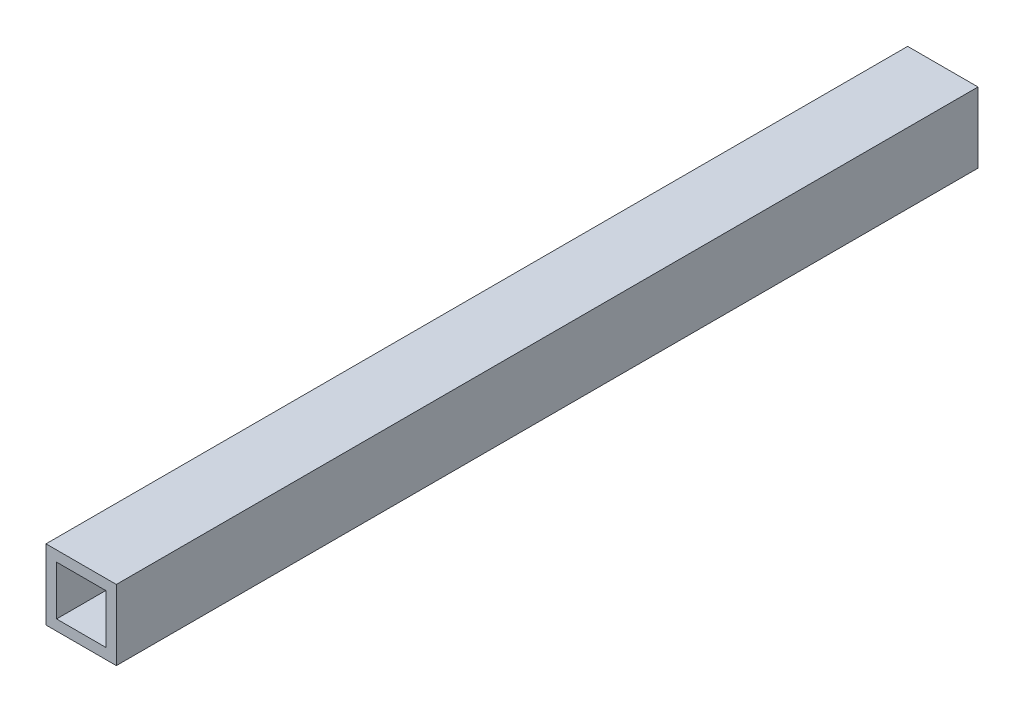
SolidWorks part; units mm, degrees
ref_plane "前视基准面" through (0, 0, 0) normal (0, 0, 1) x (1, 0, 0)
ref_plane "上视基准面" through (0, 0, 0) normal (0, 1, 0) x (1, 0, 0)
ref_plane "右视基准面" through (0, 0, 0) normal (1, 0, 0) x (0, 0, -1)
other "Configuration Table"
sketch "草图1" plane through (0, 0, 0) normal (0, 0, 1) x (1, 0, 0)
  line L0 (-9.3333, 11.0061) -> (-9.3333, -8.9939)
  line L1 (-9.3333, 11.0061) -> (10.6667, 11.0061)
  line L2 (-9.3333, -8.9939) -> (10.6667, -8.9939)
  line L3 (10.6667, 11.0061) -> (10.6667, -8.9939)
  dimension "D1" = 20
  dimension "D2" = 20
extrude "凸台-拉伸1" add sketch "草图1" along normal blind 245
sketch "草图2" plane through (0, 0, 0) normal (0, 0, -1) x (-1, 0, 0)
  line L0 (-10.6667, -8.9939) -> (-10.6667, 11.0061) construction
  line L1 (-7.6667, 8.0061) -> (6.3333, 8.0061)
  line L2 (-7.6667, 8.0061) -> (-7.6667, -5.9939)
  line L3 (-7.6667, -5.9939) -> (6.3333, -5.9939)
  line L4 (6.3333, 8.0061) -> (6.3333, -5.9939)
  line L5 (9.3333, 11.0061) -> (9.3333, -8.9939) construction
  line L6 (9.3333, -8.9939) -> (-10.6667, -8.9939) construction
  line L7 (-10.6667, 11.0061) -> (9.3333, 11.0061) construction
  dimension "D1" = 3
  dimension "D2" = 3
  dimension "D3" = 3
  dimension "D4" = 3
extrude "切除-拉伸1" cut sketch "草图2" against normal through all
